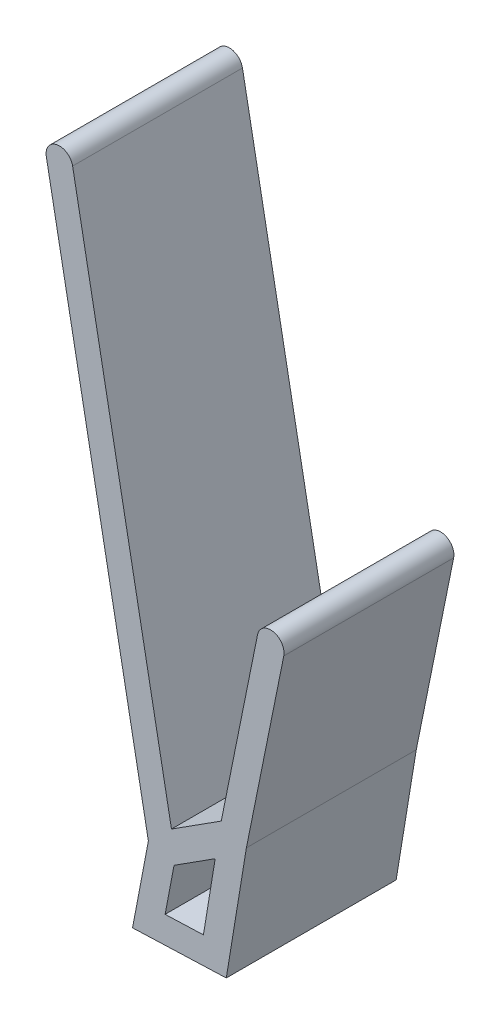
SolidWorks part; units mm, degrees
ref_plane "Front Plane" through (0, 0, 0) normal (0, 0, 1) x (1, 0, 0)
ref_plane "Top Plane" through (0, 0, 0) normal (0, 1, 0) x (1, 0, 0)
ref_plane "Right Plane" through (0, 0, 0) normal (1, 0, 0) x (0, 0, -1)
sketch "sketch - skeleton" plane through (0, 0, 0) normal (0, 0, 1) x (1, 0, 0)
  line L0 (0, 0) -> (0, -50000) construction
  line L1 (0, 0) -> (7.455, 0.2734) construction
  line L2 (9.9233, 0.3639) -> (10.6101, 4.558) construction
  line L3 (10.6101, 4.558) -> (7.9471, 2.8569) construction
  line L4 (7.9471, 2.8569) -> (7.455, 0.2734) construction
  line L5 (10.6101, 4.558) -> (12.0093, 11.478) construction
  line L6 (7.9471, 2.8569) -> (4.1146, 23.199) construction
  line L7 (7.455, 0.2734) -> (9.9233, 0.3639) construction
  line L8 (9.9233, 0.3639) -> (14.65, 0.5372) construction
  line L9 (10.6101, 4.558) -> (13.9821, 6.712) construction
  line L11 (7.9471, 2.8569) -> (5.8206, 1.4986) construction
  dimension "D1" = 92.1
  dimension "D2" = 7.46
  dimension "D3" = 2.47
  dimension "D4" = 4.25
  dimension "D5" = 78.6
  dimension "D6" = 3.16
  dimension "D7" = 7.06
  dimension "D8" = 20.7
  dimension "D10" = 46
  dimension "D11" = 111.9
  dimension "D9" = 2.63
sketch "Sketch1" plane through (0, 0, 0) normal (0, 0, 1) x (1, 0, 0)
  line L0 (8.3979, 2.5516) -> (8.0635, 0.796)
  line L1 (7.4382, 2.8574) -> (6.8464, -0.2493)
  line L2 (8.0635, 0.796) -> (9.496, 0.8485)
  line L3 (10.3506, -0.1208) -> (6.8464, -0.2493)
  line L4 (7.9471, 2.8569) -> (7.455, 0.2734) construction
  line L5 (11.5192, 11.5771) -> (10.1621, 4.8651)
  line L6 (7.455, 0.2734) -> (9.9233, 0.3639) construction
  line L8 (9.9358, 3.5339) -> (8.3979, 2.5516)
  line L9 (10.6101, 4.558) -> (7.9471, 2.8569) construction
  line L10 (9.0969, 0.8339) -> (9.1335, -0.1654) construction
  line L11 (7.2099, 1.6587) -> (8.1922, 1.4716) construction
  line L12 (8.9779, 4.1086) -> (9.5162, 3.2659) construction
  line L13 (9.9358, 3.5339) -> (9.496, 0.8485)
  line L14 (11.1021, 4.468) -> (10.3506, -0.1208)
  line L15 (9.9233, 0.3639) -> (10.6101, 4.558) construction
  line L16 (9.8006, 2.7086) -> (10.7875, 2.547) construction
  line L17 (12.4994, 11.3789) -> (11.1021, 4.468)
  line L18 (10.6101, 4.558) -> (12.0093, 11.478) construction
  line L19 (10.5977, 7.0192) -> (11.5778, 6.821) construction
  line L20 (3.6233, 23.1065) -> (7.4382, 2.8574)
  line L21 (8.3015, 3.6766) -> (4.606, 23.2916)
  line L22 (7.9471, 2.8569) -> (4.1146, 23.199) construction
  line L23 (6.0985, 9.9681) -> (7.0813, 10.1533) construction
  line L24 (8.3015, 3.6766) -> (10.1621, 4.8651)
  arc A0 (11.5192, 11.5771) -> (12.4994, 11.3789) centre (12.0093, 11.478) cw
  arc A1 (3.6233, 23.1065) -> (4.606, 23.2916) centre (4.1146, 23.199) cw
  point P3 (0, 0)
  point P7 (0, 0)
  point P8 (0, 0)
  point P14 (0, 0)
  point P15 (10.1621, 4.8651)
  point P25 (9.247, 3.6873)
  point P26 (0, 0)
  point P27 (7.701, 1.5651)
  point P28 (9.1152, 0.3342)
  point P36 (10.2941, 2.6278)
  point P38 (11.0877, 6.9201)
  point P42 (8.3979, 3.1449)
  point P44 (10.9647, 3.7887)
  point P51 (6.5899, 10.0607)
  point P52 (0, 0)
  point P57 (7.4706, 2.6852)
  dimension "D1" = 1
extrude "Boss-Extrude1" add sketch "Sketch1" along normal blind 6.35
equation "\"axle-diameter\"=2"
equation "\"switch-thickness\"=12"
equation "\"base-width\"=4.0"
equation "\"axle-bushing-radius\"=3"
equation "\"clearance\"= 0.25"
equation "\"arm-width\"=3.0"
equation "\"min-diameter\"=70"
equation "\"alpha\"=92.1"
equation "\"beta\"=26.0"
equation "\"gamma\"=78.6"
equation "\"delta\"=111.9"
equation "\"epsilon\"=46.0"
equation "\"eta\"=-228.1"
equation "\"l_AB\"=2.47"
equation "\"l_AC\"=2.63"
equation "\"l_BD\"=4.25"
equation "\"l_CD\"=3.16"
equation "\"l_CE\"=20.70"
equation "\"l_DF\"=7.06"
equation "\"l_OA\"=7.46"
equation "\"D1@sketch - skeleton\"=\"alpha\""
equation "\"D2@sketch - skeleton\"=\"l_OA\""
equation "\"D3@sketch - skeleton\"=\"l_AB\""
equation "\"D4@sketch - skeleton\"=\"l_BD\""
equation "\"D5@sketch - skeleton\"=\"gamma\""
equation "\"D6@sketch - skeleton\"=\"l_CD\""
equation "\"D7@sketch - skeleton\"=\"l_DF\""
equation "\"D8@sketch - skeleton\"=\"l_CE\""
equation "\"D10@sketch - skeleton\"=\"epsilon\""
equation "\"D11@sketch - skeleton\"=\"delta\""
equation "\"D9@sketch - skeleton\"=\"l_AC\""
